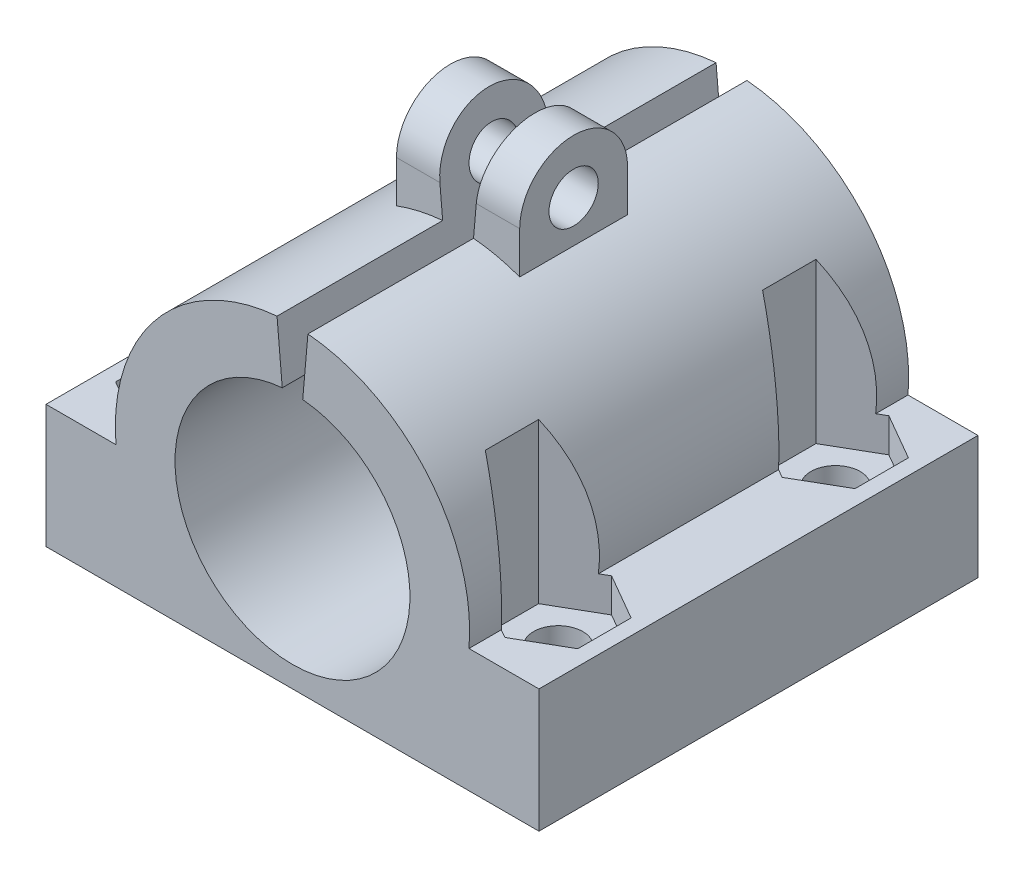
SolidWorks part; units mm, degrees
ref_plane "Front Plane" through (0, 0, 0) normal (0, 0, 1) x (1, 0, 0)
ref_plane "Top Plane" through (0, 0, 0) normal (0, 1, 0) x (1, 0, 0)
ref_plane "Right Plane" through (0, 0, 0) normal (1, 0, 0) x (0, 0, -1)
sketch "Sketch1" plane through (0, 0, 0) normal (0, 1, 0) x (1, 0, 0)
  line L1 (-16, 14.25) -> (16, 14.25)
  line L2 (-16, 14.25) -> (-16, -14.25)
  line L3 (-16, -14.25) -> (16, -14.25)
  line L4 (16, 14.25) -> (16, -14.25)
  line L5 (-16, 14.25) -> (16, -14.25) construction
  line L6 (-16, -14.25) -> (16, 14.25) construction
  point P0 (0, 0)
  dimension "D1" = 32
  dimension "D2" = 28.5
extrude "Boss-Extrude1" add sketch "Sketch1" along normal blind 8
sketch "Sketch3" plane through (0, 0, 14.25) normal (0, 0, 1) x (1, 0, 0)
  line L0 (0, 0) -> (0, 9) construction
  line L1 (-16, 0) -> (16, 0) construction
  line L2 (-7.1589, 0) -> (7.1589, 0)
  arc A0 (7.1589, 0) -> (-7.1589, 0) centre (0, 9) ccw
  dimension "D1" = 23
  dimension "D2" = 9
extrude "Boss-Extrude2" add sketch "Sketch3" against normal through all contours A0 L2
sketch "Sketch4" plane through (0, 0, 14.25) normal (0, 0, 1) x (1, 0, 0)
  line L0 (0, 20.5) -> (0, 0) construction
  line L1 (0, 9) -> (-11.5, 9) construction
  arc A0 (11.4564, 8) -> (-11.4564, 8) centre (0, 9) ccw construction
  circle A1 centre (0, 9) radius 7.625
  dimension "D1" = 15.25
  dimension "D2" = 0
extrude "Cut-Extrude2" cut sketch "Sketch4" against normal offset from surface (26.5 mm away) 2 up to face at (0, 7.4167, -14.25)
sketch "Sketch5" plane through (0, 0, -14.25) normal (0, 0, -1) x (-1, 0, 0)
  line L0 (0, 0) -> (0, 20.5) construction
  line L1 (7.625, 9) -> (-7.625, 9) construction
  arc A0 (11.4564, 8) -> (-11.4564, 8) centre (0, 9) ccw construction
  circle A1 centre (0, 9) radius 6
  circle A2 centre (0, 9) radius 7.625 construction
  circle A3 centre (0, 9) radius 7.625 construction
  dimension "D1" = 12
  dimension "D2" = 0
extrude "Cut-Extrude3" cut sketch "Sketch5" against normal through all
sketch "Sketch2" plane through (0, 8, 0) normal (0, 1, 0) x (1, 0, 0)
  line L0 (0, -14.25) -> (0, 14.25) construction
  line L1 (0, 0) -> (-16, 0) construction
  line L2 (-16, 14.25) -> (-16, -14.25) construction
  line L5 (-11.5, -14.25) -> (11.5, -14.25) construction
  line L6 (11.5, 14.25) -> (-11.5, 14.25) construction
  circle A0 centre (-12, 9) radius 1.6
  circle A1 centre (12, 9) radius 1.6
  circle A2 centre (12, -9) radius 1.6
  circle A3 centre (-12, -9) radius 1.6
  dimension "D3" = 3.2
  dimension "D1" = 12
  dimension "D2" = 9
extrude "Cut-Extrude1" cut sketch "Sketch2" against normal through all and the other way through all
sketch "Sketch6" plane through (0, 8, 0) normal (0, 1, 0) x (1, 0, 0)
  line L0 (-16, 0) -> (16, 0) construction
  line L1 (-16, 14.25) -> (-16, -14.25) construction
  line L2 (16, -14.25) -> (16, 14.25) construction
  line L3 (0, 14.25) -> (0, -14.25) construction
  line L4 (11.5, 14.25) -> (-11.5, 14.25) construction
  line L5 (-11.5, -14.25) -> (11.5, -14.25) construction
  line L6 (-12, 9) -> (-12, 12.4641) construction
  line L7 (-12, 12.4641) -> (-15, 10.7321)
  line L8 (-15, 10.7321) -> (-15, 7.2679)
  line L9 (-15, 7.2679) -> (-12, 5.5359)
  line L10 (-12, 5.5359) -> (-9, 7.2679)
  line L11 (-9, 7.2679) -> (-9, 10.7321)
  line L12 (-9, 10.7321) -> (-12, 12.4641)
  line L13 (-12, -9) -> (-12, -12.4641) construction
  line L14 (-9, -10.7321) -> (-12, -12.4641)
  line L15 (-9, -7.2679) -> (-9, -10.7321)
  line L16 (-12, -5.5359) -> (-9, -7.2679)
  line L17 (-15, -7.2679) -> (-12, -5.5359)
  line L18 (-15, -10.7321) -> (-15, -7.2679)
  line L19 (-12, -12.4641) -> (-15, -10.7321)
  line L20 (12, -9) -> (12, -12.4641) construction
  line L21 (12, 9) -> (12, 12.4641) construction
  line L22 (12, -12.4641) -> (15, -10.7321)
  line L23 (15, -10.7321) -> (15, -7.2679)
  line L24 (15, -7.2679) -> (12, -5.5359)
  line L25 (12, -5.5359) -> (9, -7.2679)
  line L26 (9, -7.2679) -> (9, -10.7321)
  line L27 (9, -10.7321) -> (12, -12.4641)
  line L28 (9, 10.7321) -> (12, 12.4641)
  line L29 (9, 7.2679) -> (9, 10.7321)
  line L30 (12, 5.5359) -> (9, 7.2679)
  line L31 (15, 7.2679) -> (12, 5.5359)
  line L32 (15, 10.7321) -> (15, 7.2679)
  line L33 (12, 12.4641) -> (15, 10.7321)
  circle A0 centre (-12, 9) radius 3 construction
  circle A1 centre (-12, -9) radius 3 construction
  circle A2 centre (12, -9) radius 3 construction
  circle A3 centre (12, 9) radius 3 construction
  circle A4 centre (-12, 9) radius 1.6 construction
  dimension "D2" = 0
  dimension "D1" = 6
extrude "Cut-Extrude4" cut sketch "Sketch6" along normal through all and the other way blind 2.2
sketch "Sketch8" plane through (0, 0, 0) normal (1, 0, 0) x (0, 0, -1)
  line L0 (0, 0) -> (0, 22.5) construction
  line L1 (-3.5, 22.5) -> (-3.5, 18.5)
  line L2 (-3.5, 18.5) -> (3.5, 18.5)
  line L3 (3.5, 18.5) -> (3.5, 22.5)
  line L4 (14.25, 20.5) -> (-14.25, 20.5) construction
  arc A0 (3.5, 22.5) -> (-3.5, 22.5) centre (0, 22.5) ccw
  circle A1 centre (0, 22.5) radius 1.6
  dimension "D1" = 7
  dimension "D4" = 3.2
  dimension "D2" = 2
  dimension "D3" = 4
extrude "Boss-Extrude3" add sketch "Sketch8" along normal blind 4 and the other way blind 4
sketch "Sketch9" plane through (0, 0, 14.25) normal (0, 0, 1) x (1, 0, 0)
  line L0 (0, 31) -> (0, 9) construction
  line L1 (0, 9) -> (1.7431, 28.9239)
  line L2 (0, 9) -> (-1.7431, 28.9239)
  arc A1 (1.7431, 28.9239) -> (-1.7431, 28.9239) centre (0, 9) ccw
  dimension "D2" = 40
  dimension "D1" = 5
extrude "Cut-Extrude5" cut sketch "Sketch9" against normal through all
equation "\"X-ROD-SPACING\"=45"
equation "\"Y-ROD-SPACING\"=75"
equation "\"Z-ROD-SPACING\"=17.5"
equation "\"Y-BED-OFFSET\"=2"
equation "\"Y-BED-ROD-INSET\"=3.5"
equation "\"T-SLOT-NUT-FILLET-RADIUS\"=0.25"
equation "\"T-SLOT-SCREW-SHAFT-RADIUS\"=1.75"
equation "\"T-SLOT-SCREW-SHAFT-CUTOUT-LENGTH\"=10.5"
equation "\"T-SLOT-NUT-DEPTH\"=4.2"
equation "\"T-SLOT-NUT-WIDTH\"=3"
equation "\"T-SLOT-NUT-END-DISTANCE\"=8"
equation "\"ACRYLIC-THICKNESS\"=10"
equation "\"ACRYLIC-THICKNESS2\"=4.5"
equation "\"ACRYLIC-TAB-CUTOUT-SIZE\"=\"ACRYLIC-THICKNESS\"+\"ACRYLIC-TAB-TOLERANCE\"*2"
equation "\"ACRYLIC-TAB-WIDTH\"=\"ACRYLIC-THICKNESS\""
equation "\"ACRYLIC-M3-HOLE\"=3.1"
equation "\"SMOOTHROD-CAP-SCREW-DISTANCE\"=20"
equation "\"FRAME-WIDTH-INNER\"=370"
equation "\"NEMA17-HOLE-SPACING\"=31"
equation "\"NEMA17-CENTRAL-CUTOUT\"=22.5"
equation "\"Z-BRACKET-REACH\"=55"
equation "\"TOP-BRACKET-SPACING\"=40"
equation "\"SMOOTHROD-X-LENGTH\"=350"
equation "\"SMOOTHROD-Y-LENGTH\"=350"
equation "\"SMOOTHROD-Z-LENGTH\"=350"
equation "\"SMOOTHROD-TIGHTENING-HEADROOM\"=1"
equation "\"LEADSCREW-Z-LENGTH\"=300"
equation "\"SCREW-LENGTH-FRAME\"=\"ACRYLIC-THICKNESS\" + 10"
equation "\"SCREW-HEAD-RADIUS\"=6"
equation "\"PRINTED-X-SMOOTHROD-DIAMETER\"=8.2"
equation "\"PRINTED-X-SMOOTHROD-CUTOUT\"=10"
equation "\"PRINTED-X-BASE-HEIGHT\"=10"
equation "\"PRINTED-LM8UU-CUTOUT-SIZE\"=15.25"
equation "\"PRINTED-LM8UU-CUTOUT-LENGTH\"=24.5"
equation "\"PRINTED-X-IDLER-HEIGHT\"=16"
equation "\"PSU-MOUNTING-WIDTH\"=95"
equation "\"PSU-MOUNTING-HEIGHT\"=177"
equation "\"Y-BELT-TO-ROD-DISTANCE\"=20"
equation "\"D3@Sketch2\"=3.2"
equation "\"D1@Sketch4\"=\"PRINTED-LM8UU-CUTOUT-SIZE\""
equation "\"D1@Sketch6\"=\"T-SLOT-NUT-WIDTH\"*2"
